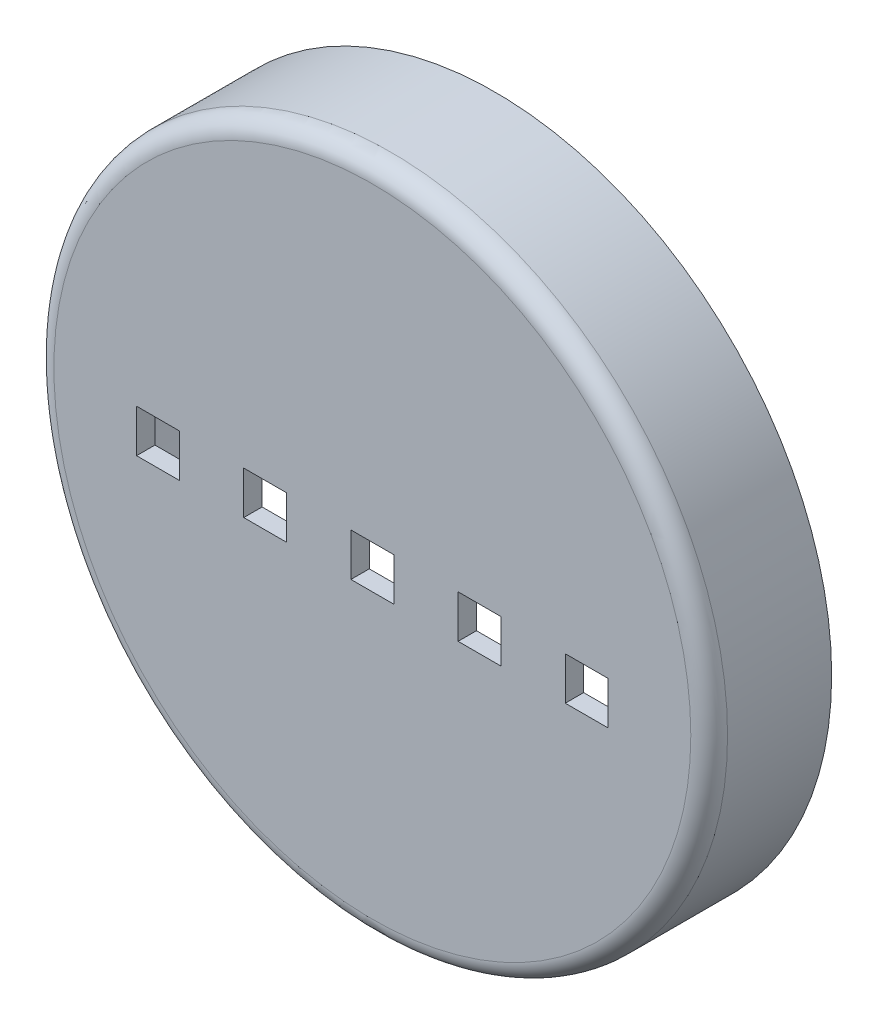
SolidWorks part; units mm, degrees
ref_plane "Front Plane" through (0, 0, 0) normal (0, 0, 1) x (1, 0, 0)
ref_plane "Top Plane" through (0, 0, 0) normal (0, 1, 0) x (1, 0, 0)
ref_plane "Right Plane" through (0, 0, 0) normal (1, 0, 0) x (0, 0, -1)
sketch "Sketch1" plane through (0, 0, 0) normal (0, 0, 1) x (1, 0, 0)
  circle A0 centre (328.3894, 629.2716) radius 55
  circle A1 centre (328.3894, 629.2716) radius 51
  dimension "D1" = 110
  dimension "D2" = 102
extrude "Boss-Extrude2" add sketch "Sketch1" along normal blind 20 contours A0
sketch "Sketch2" plane through (0, 0, 0) normal (0, 0, -1) x (-1, 0, 0)
  circle A0 centre (-328.6286, 629.3843) radius 51
  dimension "D1" = 102
extrude "Cut-Extrude1" cut sketch "Sketch2" against normal blind 17
sketch "Sketch10" plane through (0, 0, 17) normal (0, 0, -1) x (-1, 0, 0)
  line L0 (-328.3894, 627.0764) -> (-374.3894, 627.0764)
  line L1 (-378.3894, 627.0764) -> (-278.3894, 627.0764)
  line L2 (-378.3894, 627.0764) -> (-378.3894, 647.0764)
  line L3 (-378.3894, 647.0764) -> (-278.3894, 647.0764)
  line L4 (-278.3894, 627.0764) -> (-278.3894, 647.0764)
  line L6 (-331.8894, 630.5764) -> (-324.8894, 630.5764)
  line L7 (-331.8894, 630.5764) -> (-331.8894, 623.5764)
  line L8 (-331.8894, 623.5764) -> (-324.8894, 623.5764)
  line L9 (-324.8894, 630.5764) -> (-324.8894, 623.5764)
  line L10 (-314.3894, 630.5764) -> (-307.3894, 630.5764)
  line L11 (-314.3894, 630.5764) -> (-314.3894, 623.5764)
  line L12 (-314.3894, 623.5764) -> (-307.3894, 623.5764)
  line L13 (-307.3894, 630.5764) -> (-307.3894, 623.5764)
  line L14 (-296.8894, 630.5764) -> (-289.8894, 630.5764)
  line L15 (-296.8894, 630.5764) -> (-296.8894, 623.5764)
  line L16 (-296.8894, 623.5764) -> (-289.8894, 623.5764)
  line L17 (-289.8894, 630.5764) -> (-289.8894, 623.5764)
  line L18 (-349.3894, 630.5764) -> (-342.3894, 630.5764)
  line L19 (-349.3894, 630.5764) -> (-349.3894, 623.5764)
  line L20 (-349.3894, 623.5764) -> (-342.3894, 623.5764)
  line L21 (-342.3894, 630.5764) -> (-342.3894, 623.5764)
  line L22 (-366.8894, 630.5764) -> (-359.8894, 630.5764)
  line L23 (-366.8894, 630.5764) -> (-366.8894, 623.5764)
  line L24 (-366.8894, 623.5764) -> (-359.8894, 623.5764)
  line L25 (-359.8894, 630.5764) -> (-359.8894, 623.5764)
  circle A0 centre (-328.3894, 629.2716) radius 55 construction
  circle A1 centre (-374.3894, 627.0764) radius 1.5
  circle A2 centre (-282.3894, 627.0764) radius 1.5
  dimension "D5" = 3
  dimension "D7" = 3
  dimension "D1" = 100
  dimension "D2" = 50
  dimension "D3" = 20
  dimension "D4" = 2.1952
  dimension "D6" = 4
  dimension "D8" = 4
  dimension "D9" = 7
  dimension "D10" = 7
  dimension "D11" = 3.5
  dimension "D12" = 7
  dimension "D13" = 7
  dimension "D14" = 7
  dimension "D15" = 7
  dimension "D16" = 3.5
  dimension "D17" = 3.5
  dimension "D18" = 7
  dimension "D19" = 7
  dimension "D20" = 3.5
  dimension "D21" = 3.5
  dimension "D22" = 7
  dimension "D23" = 7
  dimension "D24" = 3.5
  dimension "D25" = 17.5
  dimension "D26" = 17.5
  dimension "D27" = 17.5
  dimension "D28" = 17.5
extrude "Boss-Extrude3" add sketch "Sketch10" along normal blind 10 contours A1 | A2
extrude "Cut-Extrude4" cut sketch "Sketch10<3>" against normal blind 10 contours L25 L22 L23 L1 | L25 L1 L23 L24 | L21 L18 L19 L0 | L21 L0 L19 L20 | L9 L6 L7 L0 L1 | L9 L1 L0 L7 L8 | L13 L10 L11 L1 | L17 L14 L15 L1 | L17 L1 L15 L16 | L12 L13 L10 L11 region at (363.3894, 628.8264, 17) region at (363.3894, 625.3264, 17) region at (345.8894, 628.8264, 17) region at (345.8894, 625.3264, 17) region at (328.3894, 628.8264, 17) region at (328.3894, 625.3264, 17) region at (310.8894, 628.8264, 17) region at (293.3894, 625.3264, 17) region at (293.3894, 628.8264, 17)
sketch "Sketch10<3>" plane through (0, 0, 17) normal (0, 0, -1) x (-1, 0, 0) same geometry as "Sketch10"
fillet "Fillet1" radius 3 1 edges at (383.3894, 629.2716, 20)
